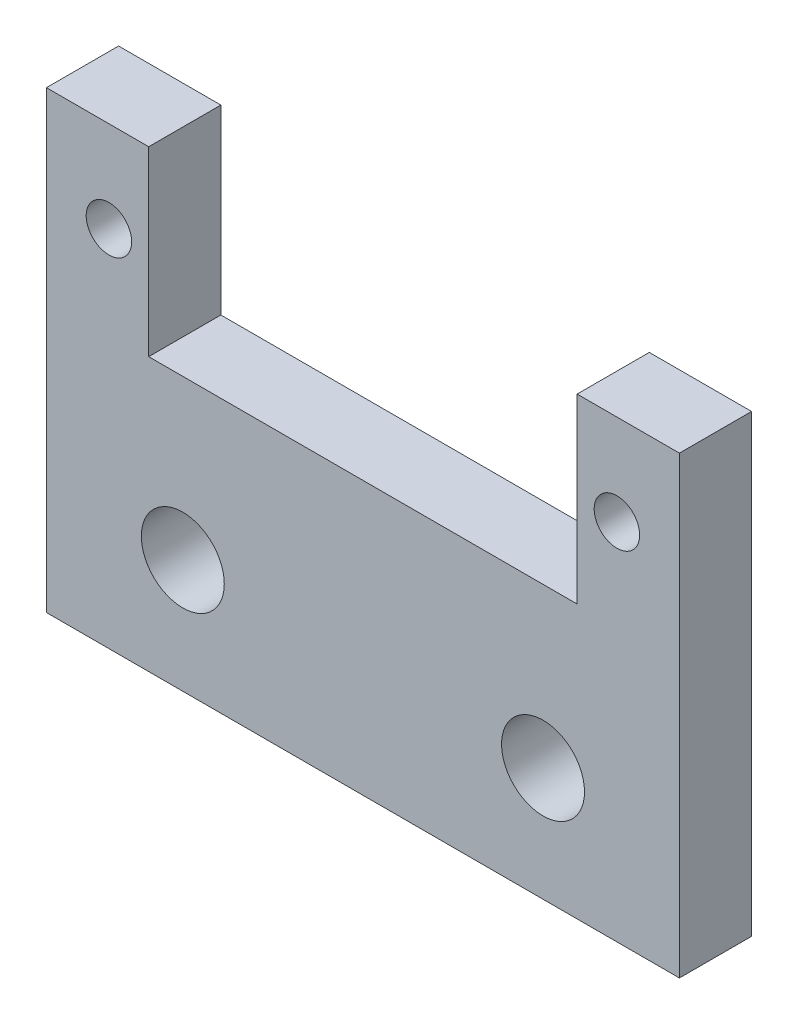
SolidWorks part; units mm, degrees
ref_plane "Front Plane" through (0, 0, 0) normal (0, 0, 1) x (1, 0, 0)
ref_plane "Top Plane" through (0, 0, 0) normal (0, 1, 0) x (1, 0, 0)
ref_plane "Right Plane" through (0, 0, 0) normal (1, 0, 0) x (0, 0, -1)
sketch "Sketch1" plane through (0, 0, 0) normal (0, 0, 1) x (1, 0, 0)
  line L0 (0, 8) -> (0, 0)
  line L1 (0, 8) -> (4.5, 8)
  line L2 (4.5, 8) -> (4.5, 0)
  line L3 (4.5, 0) -> (23.35, 0)
  line L4 (23.35, 0) -> (23.35, 8)
  line L5 (23.35, 8) -> (27.85, 8)
  line L6 (27.85, 8) -> (27.85, -12)
  line L7 (27.85, -12) -> (0, -12)
  line L8 (0, -12) -> (0, 0)
  line L12 (0, 4) -> (27.85, 4) construction
  circle A0 centre (2.75, 4) radius 1
  circle A1 centre (25.1, 4) radius 1
  circle A2 centre (6, -7) radius 1.825
  circle A3 centre (21.85, -7) radius 1.825
  dimension "D5" = 2
  dimension "D6" = 2
  dimension "D9" = 5
  dimension "D10" = 5
  dimension "D11" = 3.65
  dimension "D12" = 3.65
  dimension "D14" = 6
  dimension "D15" = 1.75
  dimension "D1" = 4.5
  dimension "D2" = 4.5
  dimension "D3" = 8
  dimension "D4" = 8
  dimension "D7" = 22.35
  dimension "D8" = 12
  dimension "D13" = 6
  dimension "D16" = 1.75
extrude "Boss-Extrude1" add sketch "Sketch1" along normal blind 3.175
